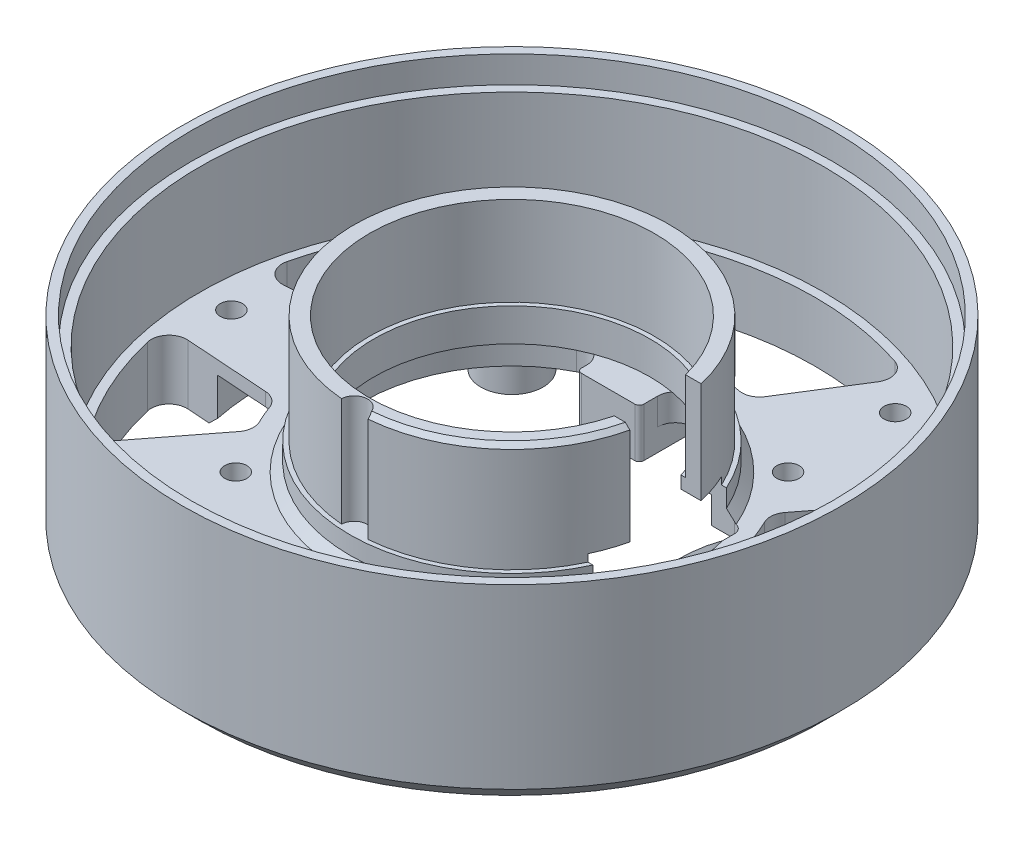
SolidWorks part; units mm, degrees
ref_plane "Front Plane" through (0, 0, 0) normal (0, 0, 1) x (1, 0, 0)
ref_plane "Top Plane" through (0, 0, 0) normal (0, 1, 0) x (1, 0, 0)
ref_plane "Right Plane" through (0, 0, 0) normal (1, 0, 0) x (0, 0, -1)
ref_axis "Axis1" through (0, 0, 0) along (0, 1, 0)
sketch "Sketch1" plane through (0, 0, 0) normal (0, 0, 1) x (1, 0, 0)
  line L0 (0, 0) -> (0, -50277.2651) construction
  line L1 (-17.7, 6) -> (-17.7, -6.2)
  line L2 (-17.7, -6.2) -> (-18.2, -6.2)
  line L3 (-18.2, -6.2) -> (-18.2, -8.2)
  line L4 (-19.2, -9.2) -> (-35, -9.2)
  line L7 (-35, -9.2) -> (-35, 3)
  line L8 (-35, 3) -> (-36, 3)
  line L9 (-36, 3) -> (-36, 6)
  line L10 (-36, 6) -> (-37, 6)
  line L11 (-37, 6) -> (-37, -13.9)
  line L12 (-35, -15.9) -> (-28, -15.9)
  line L13 (-28, -15.9) -> (-28, -10.7)
  line L14 (-28, -10.7) -> (-16.7, -10.7)
  line L23 (-16, -4) -> (-16, 6)
  line L24 (-16, 6) -> (-17.7, 6)
  line L25 (-14.9533, -4) -> (14.9533, -4) construction
  line L26 (20.75, 6) -> (-20.75, 6) construction
  line L27 (-34, 8) -> (-34, -6) construction
  line L28 (-20.75, -6) -> (20.75, -6) construction
  line L31 (-16, -4) -> (-15.5, -4)
  line L32 (11.5, -15.9) -> (-11.5, -15.9) construction
  line L37 (-16.7, -10.7) -> (-16.7, -7.7)
  line L38 (-16.7, -7.7) -> (-15.5, -7.7)
  line L42 (-37, -13.9) -> (-35, -15.9)
  line L44 (-18.2, -8.2) -> (-19.2, -9.2)
  line L50 (-15.5, -4) -> (-15.5, -7.7)
  point P6 (-18.2, -9.2)
  point P15 (-37, -15.9)
  point P31 (-31.5, -15.9)
  dimension "D1" = 35.4
  dimension "D2" = 32
  dimension "D3" = 0.5
  dimension "D4" = 3
  dimension "D5" = 1
  dimension "D6" = 1.5
  dimension "D7" = 0.2
  dimension "D8" = 2
  dimension "D9" = 3
  dimension "D10" = 72
  dimension "D11" = 1.5
  dimension "D12" = 0.5
  dimension "D13" = 63
  dimension "D14" = 1.5
revolve "Revolve1" add sketch "Sketch1" angle 360 about L0
sketch "Sketch2" plane through (0, 0, 0) normal (0, 1, 0) x (1, 0, 0)
  circle A0 centre (0, -17.7) radius 1.5
  circle A1 centre (0, 0) radius 17.7 construction
  circle A2 centre (0, 0) radius 17.7 construction
  dimension "D1" = 3
extrude "Cut-Extrude2" cut sketch "Sketch2" along normal up to next and the other way up to surface other way up to face at (0, -6.2, 18.2)
sketch "Sketch3" plane through (0, 0, 0) normal (0, 1, 0) x (1, 0, 0)
  circle A0 centre (-15.5, -15.5) radius 3.5
  circle A1 centre (15.5, -15.5) radius 3.5
  circle A2 centre (15.5, 15.5) radius 3.5
  circle A3 centre (-15.5, 15.5) radius 3.5
  dimension "D1" = 7
extrude "Boss-Extrude1" add sketch "Sketch3" against normal up to surface (4 mm away) from surface at -10.7 starting at face at (0, -10.7, 16.7)
hole_wizard "M3x0.5 Tapped Hole1" positions "Sketch4" profile "Sketch6" tap size "M3x0.5" standard "ANSI Metric" end condition through all
sketch "Sketch4" plane through (0, -14.7, 0) normal (0, -1, 0) x (-1, 0, 0)
  point P0 (-15.5, 15.5)
  point P3 (15.5, 15.5)
  point P6 (15.5, -15.5)
  point P9 (-15.5, -15.5)
sketch "Sketch6" plane through (15.5, -14.7, -15.5) normal (1, 0, 0) x (0, 0, -1)
  line L0 (0, 0) -> (0, 20.7)
  line L1 (0, 20.7) -> (1.25, 20.7)
  line L2 (1.25, 20.7) -> (1.25, 0.35)
  line L3 (1.25, 0.35) -> (1.6, 0)
  line L5 (1.6, 0) -> (0, 0)
  line L6 (-1.25, 0.35) -> (-1.6, 0) construction
  line L11 (0, -6.35) -> (0, 107.95) construction
  dimension "Thru Tap Drill Dia." = 2.5
  dimension "Thru Tap Drill Depth" = 20.7
  dimension "Near C'Sink Dia." = 3.2
  dimension "Near C'Sink Angle" = 90
cosmetic thread "Hole Thread5" parameters "D2"=3
cosmetic thread "Hole Thread6" parameters "D2"=3
cosmetic thread "Hole Thread7" parameters "D2"=3
cosmetic thread "Hole Thread8" parameters "D2"=3
sketch "Sketch7" plane through (0, 0, 0) normal (0, 1, 0) x (1, 0, 0)
  line L0 (-4.2, 18.5) -> (1.8, 12.5) construction
  line L1 (-4.2, 12) -> (1.8, 12)
  line L2 (-4.7, 12.5) -> (-4.7, 18.5)
  line L3 (-4.2, 19) -> (1.8, 19)
  line L4 (2.3, 12.5) -> (2.3, 18.5)
  arc A0 (1.8, 12) -> (2.3, 12.5) centre (1.8, 12.5) ccw
  arc A1 (-4.7, 18.5) -> (-4.2, 19) centre (-4.2, 18.5) cw
  arc A2 (1.8, 19) -> (2.3, 18.5) centre (1.8, 18.5) cw
  arc A3 (-4.2, 12) -> (-4.7, 12.5) centre (-4.2, 12.5) cw
  point P12 (-1.2, 15.5)
  dimension "D1" = 0.5
  dimension "D2" = 15.5
  dimension "D3" = 1.2
  dimension "D4" = 7
  dimension "D5" = 7
extrude "Boss-Extrude2" add sketch "Sketch7" against normal offset from surface (5.5 mm away) 1.5 from surface at -7.7 starting at face at (0, -7.7, 15.5)
sketch "Sketch10" plane through (0, 0, 0) normal (0, 1, 0) x (1, 0, 0)
  line L1 (14.5, 4) -> (17.5, 4)
  line L2 (13.5, 3) -> (13.5, -3)
  line L3 (14.5, -4) -> (17.5, -4)
  line L4 (18.5, 3) -> (18.5, -3)
  line L5 (13.5, 4) -> (18.5, -4) construction
  line L6 (13.5, -4) -> (18.5, 4) construction
  arc A0 (17.5, -4) -> (18.5, -3) centre (17.5, -3) ccw
  arc A1 (17.5, 4) -> (18.5, 3) centre (17.5, 3) cw
  arc A2 (13.5, -3) -> (14.5, -4) centre (14.5, -3) ccw
  arc A3 (14.5, 4) -> (13.5, 3) centre (14.5, 3) ccw
  circle A4 centre (0, 0) radius 16 construction
  circle A5 centre (0, 0) radius 16 construction
  point P0 (16, 0)
  point P5 (16, 0)
  dimension "D1" = 1
  dimension "D3" = 5
  dimension "D4" = 8
  dimension "D5" = 2.5
extrude "Cut-Extrude5" cut sketch "Sketch10" against normal through all both and the other way through all
chamfer "Chamfer1" distance 0.5 angle 45 1 edges at (11.5884, 6, 13.379)
hole_wizard "M3x0.5 Tapped Hole2" positions "Sketch11" profile "Sketch12" tap size "M3x0.5" standard "ANSI Metric" end condition through all
sketch "Sketch11" plane through (0, -15.9, 0) normal (0, -1, 0) x (-1, 0, 0)
  circle A0 centre (0, 0) radius 31.5 construction
  point P0 (-31.5, 0)
  dimension "D2" = 63
sketch "Sketch12" plane through (31.5, -15.9, 0) normal (1, 0, 0) x (0, 0, -1)
  line L0 (0, 0) -> (0, 21.9)
  line L1 (0, 21.9) -> (1.25, 21.9)
  line L2 (1.25, 21.9) -> (1.25, 0.35)
  line L3 (1.25, 0.35) -> (1.6, 0)
  line L5 (1.6, 0) -> (0, 0)
  line L6 (-1.25, 0.35) -> (-1.6, 0) construction
  line L11 (0, -6.35) -> (0, 107.95) construction
  dimension "Thru Tap Drill Dia." = 2.5
  dimension "Thru Tap Drill Depth" = 21.9
  dimension "Near C'Sink Dia." = 3.2
  dimension "Near C'Sink Angle" = 90
cosmetic thread "Hole Thread12" parameters "D2"=3
pattern_circular "CirPattern2" count 6 over 360 about axis through (0, 0, 0) along (0, 1, 0) of "M3x0.5 Tapped Hole2"
sketch "Sketch13" plane through (0, 0, 0) normal (0, 1, 0) x (1, 0, 0)
  line L0 (0, 0) -> (-50000, 0) construction
  line L1 (0, 0) -> (0, 50000) construction
  line L4 (-11.773, 29.3067) -> (-6.8945, 21.5451)
  line L6 (11.773, 29.3067) -> (6.8945, 21.5451)
  line L7 (11.773, -29.3067) -> (6.8945, -21.5451)
  line L8 (-11.773, -29.3067) -> (-6.8945, -21.5451)
  line L17 (19.2664, 11.3995) -> (25.0786, 18.9201)
  line L18 (31.0063, 5.364) -> (21.6421, 6.0019)
  line L19 (31.0063, -5.364) -> (21.6421, -6.0019)
  line L20 (19.2664, -11.3995) -> (25.0786, -18.9201)
  line L21 (-19.2664, -11.3995) -> (-25.0786, -18.9201)
  line L22 (-31.0063, -5.364) -> (-21.6421, -6.0019)
  line L23 (-31.0063, 5.364) -> (-21.6421, 6.0019)
  line L24 (-19.2664, 11.3995) -> (-25.0786, 18.9201)
  arc A0 (-10.7097, 32.2692) -> (10.7097, 32.2692) centre (0, 0) cw
  arc A5 (-4.7528, 20.6604) -> (4.7528, 20.6604) centre (0, 0) cw
  circle A16 centre (0, 0) radius 35 construction
  arc A17 (-4.7528, -20.6604) -> (4.7528, -20.6604) centre (0, 0) ccw
  arc A18 (-10.7097, -32.2692) -> (10.7097, -32.2692) centre (0, 0) ccw
  arc A27 (19.0516, 9.2992) -> (19.9006, 7.3079) centre (0, 0) cw
  arc A28 (28.3274, 18.8032) -> (33.0887, 7.8193) centre (0, 0) cw
  arc A29 (28.3274, -18.8032) -> (33.0887, -7.8193) centre (0, 0) ccw
  arc A30 (19.0516, -9.2992) -> (19.9006, -7.3079) centre (0, 0) ccw
  arc A31 (-19.0516, -9.2992) -> (-19.9006, -7.3079) centre (0, 0) cw
  arc A32 (-28.3274, -18.8032) -> (-33.0887, -7.8193) centre (0, 0) cw
  arc A33 (-28.3274, 18.8032) -> (-33.0887, 7.8193) centre (0, 0) ccw
  arc A34 (-19.0516, 9.2992) -> (-19.9006, 7.3079) centre (0, 0) ccw
  arc A35 (-19.9006, 7.3079) -> (-21.6421, 6.0019) centre (-21.778, 7.9973) cw
  arc A36 (-19.0516, 9.2992) -> (-19.2664, 11.3995) centre (-20.8489, 10.1765) ccw
  arc A37 (-33.0887, 7.8193) -> (-31.0063, 5.364) centre (-31.1423, 7.3593) ccw
  arc A38 (-28.3274, 18.8032) -> (-25.0786, 18.9201) centre (-26.6611, 17.6971) cw
  arc A39 (-33.0887, -7.8193) -> (-31.0063, -5.364) centre (-31.1423, -7.3593) cw
  arc A40 (-28.3274, -18.8032) -> (-25.0786, -18.9201) centre (-26.6611, -17.6971) ccw
  arc A41 (-19.9006, -7.3079) -> (-21.6421, -6.0019) centre (-21.778, -7.9973) ccw
  arc A42 (-19.0516, -9.2992) -> (-19.2664, -11.3995) centre (-20.8489, -10.1765) cw
  arc A43 (19.9006, -7.3079) -> (21.6421, -6.0019) centre (21.778, -7.9973) cw
  arc A44 (19.0516, -9.2992) -> (19.2664, -11.3995) centre (20.8489, -10.1765) ccw
  arc A45 (33.0887, -7.8193) -> (31.0063, -5.364) centre (31.1423, -7.3593) ccw
  arc A46 (28.3274, -18.8032) -> (25.0786, -18.9201) centre (26.6611, -17.6971) cw
  arc A47 (33.0887, 7.8193) -> (31.0063, 5.364) centre (31.1423, 7.3593) cw
  arc A48 (28.3274, 18.8032) -> (25.0786, 18.9201) centre (26.6611, 17.6971) ccw
  arc A49 (10.7097, -32.2692) -> (11.773, -29.3067) centre (10.0797, -30.371) ccw
  arc A50 (-10.7097, -32.2692) -> (-11.773, -29.3067) centre (-10.0797, -30.371) cw
  arc A51 (4.7528, -20.6604) -> (6.8945, -21.5451) centre (5.2012, -22.6095) cw
  arc A52 (-4.7528, -20.6604) -> (-6.8945, -21.5451) centre (-5.2012, -22.6095) ccw
  arc A53 (19.9006, 7.3079) -> (21.6421, 6.0019) centre (21.778, 7.9973) ccw
  arc A54 (4.7528, 20.6604) -> (6.8945, 21.5451) centre (5.2012, 22.6095) ccw
  arc A55 (-4.7528, 20.6604) -> (-6.8945, 21.5451) centre (-5.2012, 22.6095) cw
  arc A56 (10.7097, 32.2692) -> (11.773, 29.3067) centre (10.0797, 30.371) cw
  arc A57 (19.0516, 9.2992) -> (19.2664, 11.3995) centre (20.8489, 10.1765) cw
  arc A58 (-10.7097, 32.2692) -> (-11.773, 29.3067) centre (-10.0797, 30.371) ccw
  arc A59 (-4.6855, 18.6195) -> (-2.7641, 19) centre (0, 0) ccw construction
  point P9 (0, 21.2)
  point P10 (0, 34)
  point P50 (-20.3055, 6.093)
  point P53 (-18.4823, 10.3849)
  point P56 (-33.602, 5.1871)
  point P59 (-26.7125, 21.0343)
  point P62 (-33.602, -5.1871)
  point P65 (-26.7125, -21.0343)
  point P68 (-20.3055, -6.093)
  point P71 (-18.4823, -10.3849)
  point P74 (20.3055, -6.093)
  point P77 (18.4823, -10.3849)
  point P80 (33.602, -5.1871)
  point P83 (26.7125, -21.0343)
  point P86 (33.602, 5.1871)
  point P89 (26.7125, 21.0343)
  point P92 (13.0786, -31.3839)
  point P95 (-13.0786, -31.3839)
  point P98 (6.1118, -20.2999)
  point P101 (-6.1118, -20.2999)
  point P104 (20.3055, 6.093)
  point P107 (6.1118, 20.2999)
  point P110 (-6.1118, 20.2999)
  point P113 (13.0786, 31.3839)
  point P116 (18.4823, 10.3849)
  point P119 (-13.0786, 31.3839)
  dimension "D1" = 2
  dimension "D2" = 1
  dimension "D3" = 2
extrude "Cut-Extrude6" cut sketch "Sketch13" against normal through all
fillet "Fillet1" radius 2 2 edges at (2.3, -9.2, -16.5409) (-4.7, -9.2, -16.025)
sketch "Sketch14" plane through (0, 0, 0) normal (0, 1, 0) x (1, 0, 0)
  line L0 (0, 0) -> (13.0895, 0) construction
  line L1 (18.5, 3) -> (18.5, -3) construction
  line L6 (8.6789, -7.5) -> (17.5, -7.5)
  line L7 (7.6789, -6.5) -> (7.6789, 6.5)
  line L8 (8.6789, 7.5) -> (17.5, 7.5)
  line L9 (18.5, -6.5) -> (18.5, 6.5)
  line L10 (7.6789, -7.5) -> (18.5, 7.5) construction
  line L11 (7.6789, 7.5) -> (18.5, -7.5) construction
  arc A7 (17.5, -7.5) -> (18.5, -6.5) centre (17.5, -6.5) ccw
  arc A8 (7.6789, 6.5) -> (8.6789, 7.5) centre (8.6789, 6.5) cw
  arc A9 (8.6789, -7.5) -> (7.6789, -6.5) centre (8.6789, -6.5) cw
  arc A10 (17.5, 7.5) -> (18.5, 6.5) centre (17.5, 6.5) cw
  dimension "D1" = 1
  dimension "D2" = 13
extrude "Cut-Extrude7" cut sketch "Sketch14" along normal offset from surface 11.38 and the other way through all from surface
sketch "Sketch15" plane through (0, -10.7, 0) normal (0, -1, 0) x (1, 0, 0)
  line L1 (13.5647, 7.5) -> (14.9211, 7.5)
  line L12 (13.5647, 7.5) -> (14.9211, 7.5)
  arc A1 (14.9211, 7.5) -> (-7.6116, -14.8645) centre (0, 0) ccw
  arc A9 (-7.6116, -14.8645) -> (-5.3403, -14.551) centre (-6.7, -13.0843) ccw
  arc A10 (-7.6116, -14.8645) -> (-5.3403, -14.551) centre (-6.7, -13.0843) ccw
  arc A11 (13.5647, 7.5) -> (-5.3403, -14.551) centre (0, 0) ccw
  arc A12 (13.5647, 7.5) -> (-5.3403, -14.551) centre (0, 0) ccw
  arc A21 (14.9211, 7.5) -> (-7.6116, -14.8645) centre (0, 0) ccw
  dimension "D1" = 0
extrude "Boss-Extrude3" [suppressed] add sketch "Sketch15" against normal up to surface (3 mm away)
chamfer "Chamfer2" distance 1 angle 45 6 edges at (28, -15.9, 0) (17.1305, -15.9, 22.1482) (-17.1305, -15.9, 22.1482) (-28, -15.9, 0) (-17.1305, -15.9, -22.1482) (17.1305, -15.9, -22.1482)
sketch "Sketch16" plane through (0, 0, 0) normal (0, 0, 1) x (1, 0, 0)
  line L0 (-17.7, -6.2) -> (-18.2, -6.2)
  line L1 (-18.2, -6.2) -> (-18.2, -8.2)
  line L2 (-18.2, -8.2) -> (-19.2, -9.2)
  line L3 (-19.2, -9.2) -> (-23.3334, -9.2)
  line L4 (-19.2, -9.2) -> (-35, -9.2) construction
  line L5 (-23.3334, -9.2) -> (-23.3334, -3.0666)
  line L6 (-23.3334, -3.0666) -> (-17.7, -3.0666)
  line L7 (-17.7, 6) -> (-17.7, -6.2) construction
  line L8 (-17.7, -3.0666) -> (-17.7, -6.2)
revolve "Cut-Revolve1" cut sketch "Sketch16" angle 360 about axis through (0, 0, 0) along (0, 1, 0)
fillet "Fillet2" [suppressed] radius 0.5
